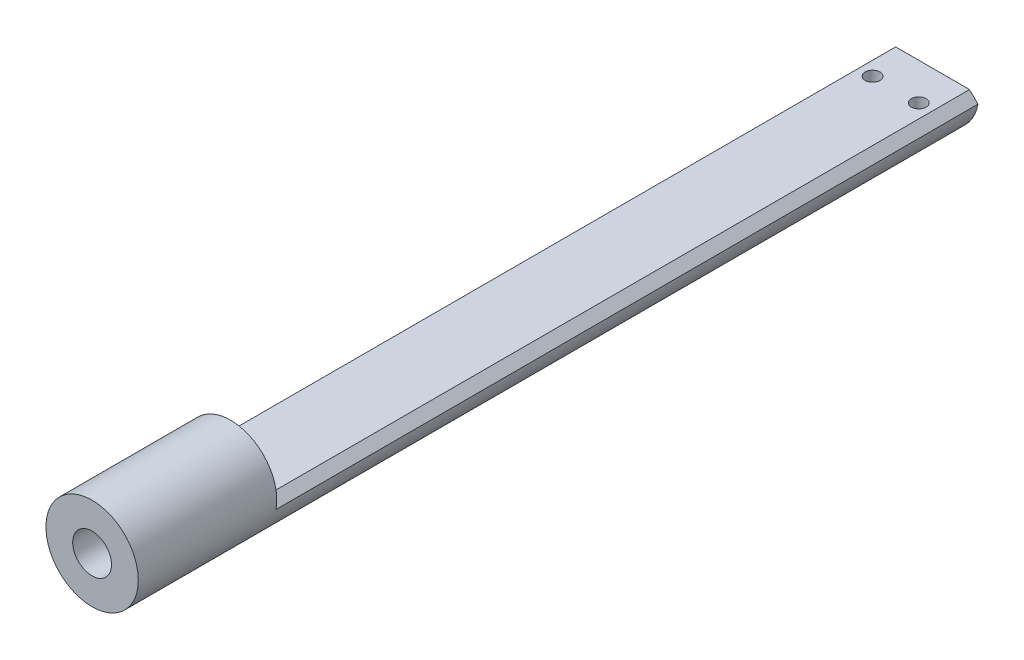
SolidWorks part; units mm, degrees
material "7050-T73510"
ref_plane "Plano frontal" through (0, 0, 0) normal (0, 0, 1) x (1, 0, 0)
ref_plane "Plano superior" through (0, 0, 0) normal (0, 1, 0) x (1, 0, 0)
ref_plane "Plano direito" through (0, 0, 0) normal (1, 0, 0) x (0, 0, -1)
sketch "Esboço1" plane through (0, 0, 0) normal (0, 0, 1) x (1, 0, 0)
  circle A0 centre (0, 0) radius 5
  dimension "D1" = 10
extrude "Ressalto-extrusão1" add sketch "Esboço1" along normal blind 91
sketch "Esboço10" plane through (0, 0, 0) normal (0, 0, -1) x (-1, 0, 0)
  line L0 (-5, 0) -> (5, 0)
  arc A0 (5, 0) -> (-5, 0) centre (0, 0) ccw
  dimension "D1" = 10
extrude "Corte-extrusão2" cut sketch "Esboço10" against normal offset from surface (76 mm away) 15 up to face at (5, 0, 91)
hole_wizard "Furo roscado de M51" positions "3DSketch6" profile "Esboço11" tap size "M5" standard "ISO"
sketch3d "3DSketch6"
  line L0 (0, 0, 91) -> (0, 0, 76) construction
  point P0 (0, 0, 91)
cosmetic thread "Rosca de furo1" parameters "D1"=10, "D2"=5
sketch "Esboço11" plane through (0, 0, 91) normal (1, 0, 0) x (0, -1, 0)
  line L0 (0, 0) -> (0, 14)
  line L1 (0, 14) -> (2.1, 12.7382)
  line L2 (2.1, 12.7382) -> (2.1, 0)
  line L5 (2.1, 0) -> (0, 0)
  line L10 (0, 14) -> (-2.1, 12.7382) construction
  line L11 (0, -6.35) -> (0, 107.95) construction
  dimension "Tap Drill Dia." = 4.2
  dimension "Tap Drill Depth" = 14
  dimension "Drill Angle" = 118
sketch "Esboço12" plane through (0, 0, 91) normal (0, 0, 1) x (1, 0, 0)
  point P0 (0, 0)
chamfer "Chanfro1" distance 1 2 edges at (-5, 0, 38) (5, 0, 38)
sketch "Esboço13" plane through (0, 0, 0) normal (0, 0, -1) x (-1, 0, 0)
  line L0 (-4, 0) -> (4, 0) construction
  line L2 (2.4749, -2.4749) -> (0, 0) construction
  line L3 (0, 0) -> (-2.4749, -2.4749) construction
  arc A0 (3.5, 0) -> (-3.5, 0) centre (0, 0) cw construction
  dimension "D1" = 3.5
  dimension "D2" = 45
sketch "Esboço14" plane through (0, 0, 0) normal (0, 1, 0) x (1, 0, 0)
  line L0 (-2.5, 0) -> (2.5, 0)
  line L1 (4, 0) -> (-4, 0) construction
  line L2 (-2.5, 0) -> (-2.5, -4) construction
  line L3 (-2.5, -4) -> (-2.5, -7) construction
  line L4 (-2.5, -4) -> (2.5, -4) construction
  line L5 (-2.5, -7) -> (2.5, -7) construction
  point P0 (0, 0)
  point P5 (0, 0)
  dimension "D1" = 5
  dimension "D2" = 4
  dimension "D3" = 3
hole_wizard "Broca de rosquear para tarraxa de M21" positions "3DSketch7" profile "Esboço15" hole size "M2" standard "ISO" end condition through all
sketch3d "3DSketch7"
  point P0 (-2.5, 0, 4)
  point P9 (2.5, 0, 4)
  point P14 (0, 0, 0)
  point P15 (0, 0, 0)
sketch "Esboço15" plane through (-2.5, 0, 4) normal (1, 0, 0) x (0, 0, 1)
  line L0 (0, 0) -> (0, 5)
  line L1 (0, 5) -> (0.8, 5)
  line L2 (0.8, 5) -> (0.8, 0)
  line L5 (0.8, 0) -> (0, 0)
  line L11 (0, -6.35) -> (0, 107.95) construction
  dimension "Thru Hole Dia." = 1.6
  dimension "Thru Hole Depth" = 5
sketch "Esboço16" plane through (0, 0, 91) normal (0, 0, 1) x (1, 0, 0)
  circle A0 centre (0, 0) radius 5.1
  circle A1 centre (0, 0) radius 5
  circle A2 centre (0, 0) radius 5 construction
  dimension "D1" = 10.2
sketch "Esboço17" plane through (0, 0, 0) normal (0, 1, 0) x (1, 0, 0)
  line L0 (4, -76) -> (4, 0) construction
  line L1 (-4, 0) -> (4, 0)
  line L2 (-4, 0) -> (-4, -6)
  line L3 (-4, -6) -> (4, -6)
  line L4 (4, 0) -> (4, -6)
  dimension "D1" = 6
